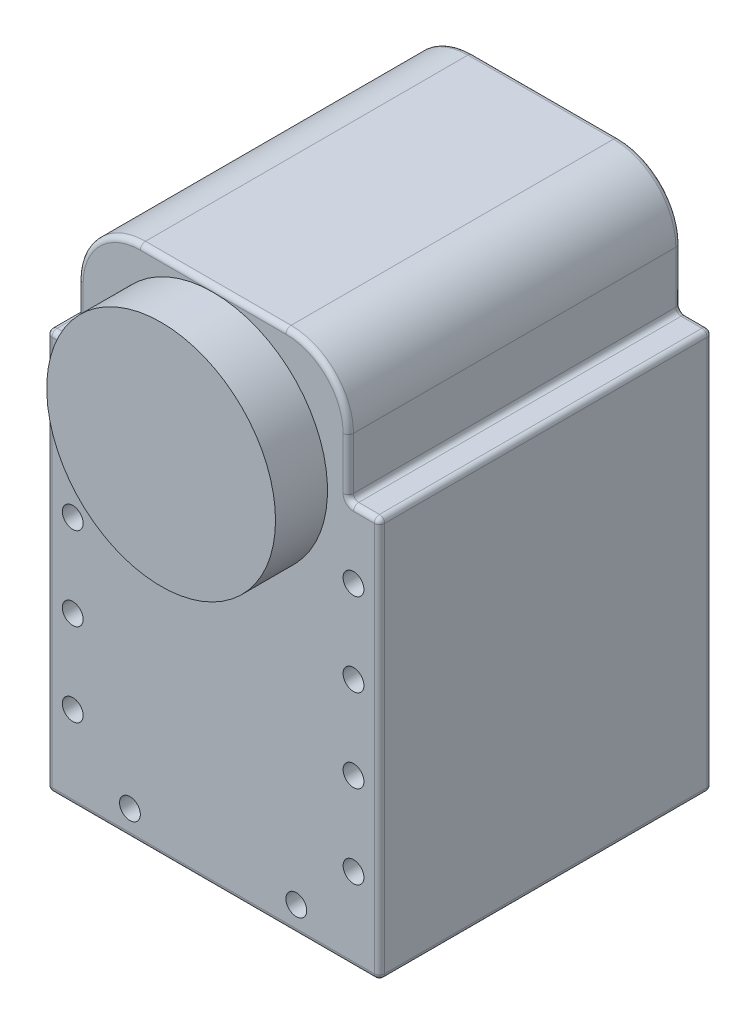
SolidWorks part; units mm, degrees
material "CA"
ref_plane "Ön Düzlem" through (0, 0, 0) normal (0, 0, 1) x (1, 0, 0)
ref_plane "Üst Düzlem" through (0, 0, 0) normal (0, 1, 0) x (1, 0, 0)
ref_plane "Sağ Düzlem" through (0, 0, 0) normal (1, 0, 0) x (0, 0, -1)
sketch "Çizim1" plane through (0, 0, 0) normal (0, 0, 1) x (1, 0, 0)
  line L1 (-16, 25) -> (16, 25)
  line L2 (-16, 25) -> (-16, -25)
  line L3 (-16, -25) -> (16, -25)
  line L4 (16, 25) -> (16, -25)
  line L5 (-16, 25) -> (16, -25) construction
  line L6 (-16, -25) -> (16, 25) construction
  point P0 (0, 0)
  dimension "D1" = 32
  dimension "D2" = 50
extrude "Yükseklik-Ekstrüzyon1" add sketch "Çizim1" along normal blind 32
sketch "Çizim2" plane through (0, 0, 32) normal (0, 0, 1) x (1, 0, 0)
  line L2 (-13, 25) -> (-13, 13.5)
  line L5 (16, 25) -> (-16, 25) construction
  line L6 (-16, -25) -> (16, -25) construction
  line L7 (-13, 13.5) -> (-16, 13.5)
  line L8 (-16, 25) -> (-16, -25) construction
  line L9 (-16, 13.5) -> (-16, 25)
  line L10 (-16, 25) -> (-13, 25)
  circle A0 centre (-8, -22.5) radius 1
  circle A1 centre (-13.5, -17) radius 1
  circle A2 centre (-13.5, -9) radius 1
  circle A3 centre (-13.5, -1) radius 1
  circle A4 centre (-13.5, 7) radius 1
  point P0 (0, 19.25)
  dimension "D6" = 2
  dimension "D2" = 11.5
  dimension "D3" = 3
  dimension "D4" = 5.75
  dimension "D7" = 8
  dimension "D8" = 8
  dimension "D9" = 8
  dimension "D10" = 8
  dimension "D11" = 6.5
  dimension "D12" = 2.5
  dimension "D13" = 2.5
extrude "Kes-Ekstrüzyon1" cut sketch "Çizim2" against normal blind 32
mirror "Aynalama1" about plane through (0, 0, 0) normal (1, 0, 0) of "Kes-Ekstrüzyon1"
fillet "Radyus2" radius 6 2 edges at (13, 25, 16) (-13, 25, 16)
sketch "Çizim3" plane through (0, 0, 32) normal (0, 0, 1) x (1, 0, 0)
  circle A0 centre (0, 13.5) radius 11
  dimension "D1" = 22
extrude "Yükseklik-Ekstrüzyon2" add sketch "Çizim3" along normal blind 5
sketch "Çizim4" plane through (0, 0, 0) normal (0, 0, -1) x (-1, 0, 0)
  circle A0 centre (0, 13.5) radius 5.5
  dimension "D1" = 11
extrude "Yükseklik-Ekstrüzyon3" add sketch "Çizim4" along normal blind 3
fillet "Radyus3" radius 0.5 27 edges at (14.5, 13.5, 32) (-14.5, 13.5, 32) (14.5, 13.5, 0) (-14.5, 13.5, 0) (13, 16.25, 32) (11.2426, 23.2426, 32) (-13, 16.25, 32) (-11.2426, 23.2426, 32) (13, 16.25, 0) (11.2426, 23.2426, 0) (0, 25, 0) (-11.2426, 23.2426, 0) (16, -5.75, 0) (0, -25, 0) (16, -25, 16) (13, 13.5, 16) (16, 13.5, 16) (16, -5.75, 32) (0, -25, 32) (-16, -5.75, 32) (0, 25, 32) (-16, -25, 16) (5.5, 13.5, 0) (-13, 13.5, 16) (-16, 13.5, 16) (-13, 16.25, 0) (-16, -5.75, 0)
ref_plane "Düzlem1" through (0, 0, 16) normal (0, 0, 1) x (1, 0, 0)
sketch "Çizim5" plane through (0, 0, 16) normal (0, 0, 1) x (1, 0, 0)
  line L1 (-15.5, 13) -> (15.5, 13)
  line L2 (-15.5, 13) -> (-15.5, -24.5)
  line L3 (-15.5, -24.5) -> (15.5, -24.5)
  line L4 (15.5, 13) -> (15.5, -24.5)
extrude "Yükseklik-Ekstrüzyon4" add sketch "Çizim5" along normal blind 13 and the other way blind 13
